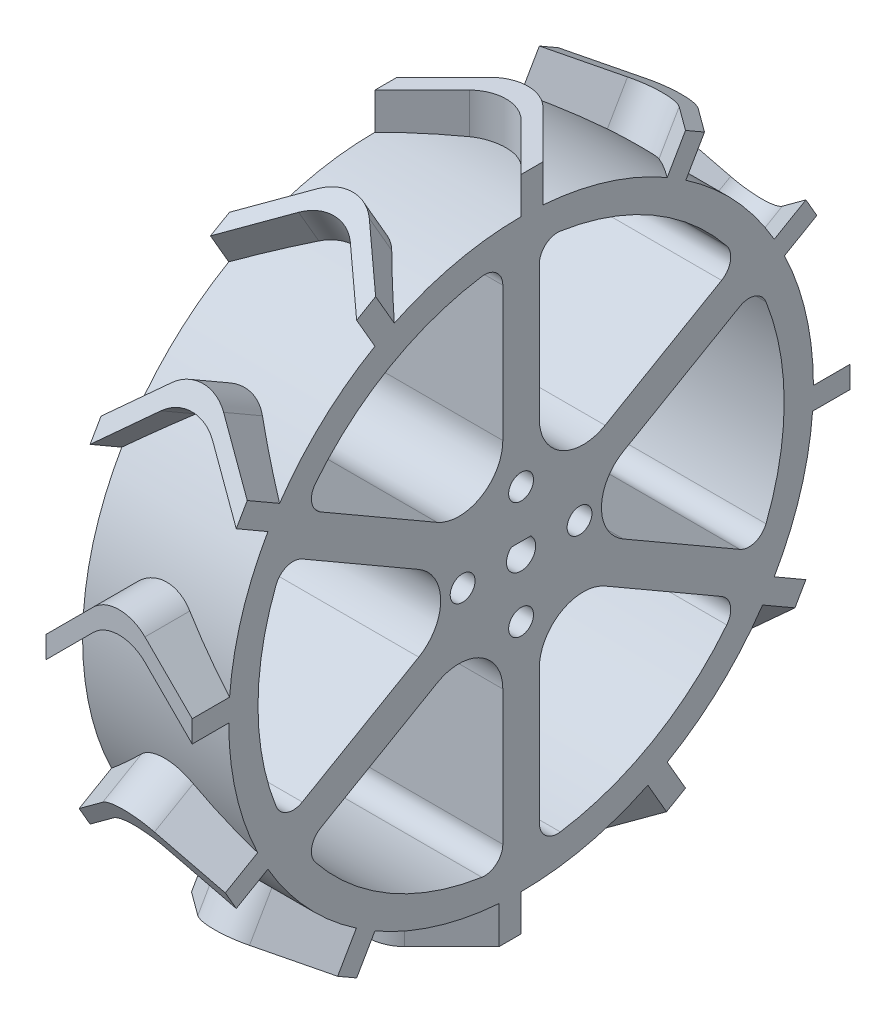
SolidWorks part; units mm, degrees
material "PLA 15%"
ref_plane "Front Plane" through (0, 0, 0) normal (0, 0, 1) x (1, 0, 0)
ref_plane "Top Plane" through (0, 0, 0) normal (0, 1, 0) x (1, 0, 0)
ref_plane "Right Plane" through (0, 0, 0) normal (1, 0, 0) x (0, 0, -1)
sketch "Sketch2" plane through (0, 0, 0) normal (1, 0, 0) x (0, 0, -1)
  circle A2 centre (0, 0) radius 40
  dimension "D1" = 80
extrude "Boss-Extrude1" add sketch "Sketch2" along normal blind 20
sketch "Sketch4" plane through (0, 0, 0) normal (0, 1, 0) x (1, 0, 0)
  line L8 (0, 0) -> (20, 0) construction
  line L9 (20, -40) -> (20, 40) construction
  line L10 (0, 0) -> (6.4645, 6.4645)
  line L11 (13.5355, 6.4645) -> (20, 0)
  line L12 (20, 0) -> (20, 3)
  line L13 (20, 3) -> (13.5355, 9.4645)
  line L14 (6.4645, 9.4645) -> (0, 3)
  line L15 (0, 40) -> (0, -40) construction
  line L16 (0, 3) -> (0, 0)
  arc A0 (13.5355, 9.4645) -> (6.4645, 9.4645) centre (10, 5.9289) ccw
  arc A1 (6.4645, 6.4645) -> (13.5355, 6.4645) centre (10, 2.9289) cw
  point P4 (10, 0)
  point P18 (10, 13)
  point P21 (10, 10)
  dimension "D3" = 5
  dimension "D1" = 3
  dimension "D2" = 3
  dimension "D4" = 10
extrude "Boss-Extrude2" add sketch "Sketch4" along normal blind 45
pattern_circular "CirPattern2" count 12 over 360 about axis through (20, 0, 0) along (-1, 0, 0) of "Boss-Extrude2"
sketch "Sketch5" plane through (0, 0, 0) normal (-1, 0, 0) x (0, 0, 1)
  line L0 (0, 0) -> (0, 40) construction
  line L1 (0, 0) -> (34.641, 20) construction
  line L6 (2.5, 33.1248) -> (2.5, 4.3301)
  line L8 (27.4369, 18.7274) -> (2.5, 4.3301)
  circle A0 centre (0, 0) radius 40 construction
  arc A2 (5.3731, 35.5968) -> (28.1411, 22.4517) centre (0, 0) cw
  arc A6 (28.1411, 22.4517) -> (27.4369, 18.7274) centre (26.1869, 20.8925) cw
  arc A7 (5.3731, 35.5968) -> (2.5, 33.1248) centre (5, 33.1248) ccw
  circle A10 centre (0, 0) radius 40 construction
  point P11 (0, 35.9131)
  point P22 (2.5, 35.9131)
  dimension "D1" = 2.5
  dimension "D2" = 4
  dimension "D8" = 2.5
  dimension "D7" = 2.5
  dimension "D9" = 60
extrude "Cut-Extrude3" cut sketch "Sketch5" against normal up to next
fillet "Fillet1" radius 6 1 edges at (10, 4.3301, 2.5)
pattern_circular "CirPattern3" count 6 over 360 about axis through (0, 0, 0) along (1, 0, 0) of "Cut-Extrude3", "Fillet1"
sketch "Sketch6" plane through (0, 0, 0) normal (-1, 0, 0) x (0, 0, 1)
  circle A0 centre (0, 8) radius 1.7
  circle A1 centre (8, 0) radius 1.7
  circle A2 centre (0, -8) radius 1.7
  circle A3 centre (-8, 0) radius 1.7
  point P0 (0, 0)
  point P13 (0, 0)
  dimension "D1" = 3.4
  dimension "D2" = 8
  dimension "D3" = 4
extrude "Cut-Extrude4" cut sketch "Sketch6" against normal up to next
sketch "Sketch8" plane through (0, 0, 0) normal (1, 0, 0) x (0, 0, -1)
  line L0 (1.3229, 1.5) -> (-1.3229, 1.5)
  arc A0 (1.3229, 1.5) -> (-1.3229, 1.5) centre (0, 0) cw
  point P4 (0, -2)
  point P5 (0, 0)
  dimension "D1" = 2
  dimension "D2" = 3.5
extrude "Cut-Extrude6" cut sketch "Sketch8" along normal through all both and the other way through all contours A0 L0
